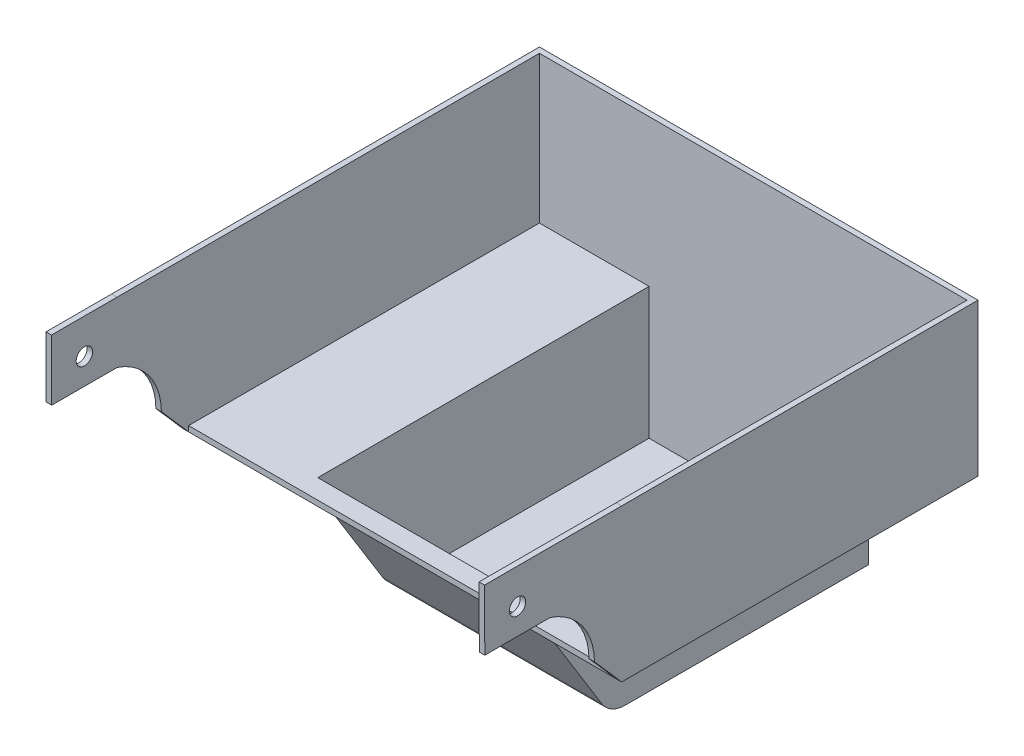
SolidWorks part; units mm, degrees
ref_plane "前视基准面" through (0, 0, 0) normal (0, 0, 1) x (1, 0, 0)
ref_plane "上视基准面" through (0, 0, 0) normal (0, 1, 0) x (1, 0, 0)
ref_plane "右视基准面" through (0, 0, 0) normal (1, 0, 0) x (0, 0, -1)
sketch "草图1" plane through (0, 0, 0) normal (0, 0, 1) x (1, 0, 0)
  line L0 (0, 151.2367) -> (0, -136.5371) construction
  line L1 (-80, 0) -> (-40, 0)
  line L2 (-80, 0) -> (-80, 55.63)
  line L3 (-40, -48) -> (40, -48)
  line L4 (-40, -48) -> (-40, 0)
  line L5 (40, 0) -> (40, -48)
  line L6 (40, 0) -> (80, 0)
  line L7 (-80, 55.63) -> (80, 55.63)
  line L8 (80, 55.63) -> (80, 0)
  point P6 (0, 0)
  point P10 (0, -48)
  dimension "D1" = 160
  dimension "D2" = 55.63
  dimension "D3" = 80
  dimension "D4" = 48
extrude "凸台-拉伸1" add sketch "草图1" along normal blind 124
sketch "草图2" plane through (0, 0, 124) normal (0, 0, 1) x (1, 0, 0)
  line L1 (-80, 0) -> (80, 0)
  line L2 (-80, 0) -> (-80, 55.63)
  line L3 (-80, 55.63) -> (80, 55.63)
  line L4 (80, 0) -> (80, 55.63)
extrude "凸台-拉伸2" add sketch "草图2" along normal blind 6
sketch "草图4" plane through (-40, 0, 0) normal (-1, 0, 0) x (0, 0, 1)
  line L0 (124, 0) -> (97.2566, -43.2585)
  line L1 (124, -48) -> (0, -48) construction
  line L2 (88.7508, -48) -> (88.7508, -53.7264)
  line L3 (88.7508, -53.7264) -> (126.101, -53.7264)
  line L4 (126.101, -53.7264) -> (126.101, 0)
  line L5 (130, 0) -> (0, 0) construction
  line L6 (126.101, 0) -> (124, 0)
  arc A0 (97.2566, -43.2585) -> (88.7508, -48) centre (88.7508, -38) cw
  point P8 (94.3253, -48)
extrude "切除-拉伸1" cut sketch "草图4" against normal through all both and the other way through all
shell "抽壳1" thickness 2 removed face at (0, 55.63, 65)
sketch "草图5" plane through (0, 0, 130) normal (0, 0, 1) x (1, 0, 0)
  line L0 (0, 59.9108) -> (0, -11.2976) construction
sketch "草图6" plane through (0, 0, 128) normal (0, 0, -1) x (-1, 0, 0)
  line L1 (78, 55.63) -> (-78, 55.63)
  line L2 (78, 55.63) -> (78, 2)
  line L3 (78, 2) -> (-78, 2)
  line L4 (-78, 55.63) -> (-78, 2)
extrude "切除-拉伸2" cut sketch "草图6" against normal blind 3
sketch "草图7" plane through (-80, 0, 0) normal (-1, 0, 0) x (0, 0, 1)
  line L0 (130, 55.63) -> (156.0921, 55.63)
  line L1 (156.0921, 55.63) -> (156.0921, 29.8201)
  line L2 (156.0921, 29.8201) -> (130, 0)
  line L3 (130, 0) -> (130, 55.63)
extrude "凸台-拉伸3" add sketch "草图7" against normal blind 2
sketch "草图8" plane through (-80, 0, 0) normal (-1, 0, 0) x (0, 0, 1)
  circle A0 centre (163.3344, 11.15) radius 23.4056
extrude "切除-拉伸3" cut sketch "草图8" against normal through all
sketch "草图9" plane through (-80, 0, 0) normal (-1, 0, 0) x (0, 0, 1)
  line L0 (156.0921, 33.407) -> (179.9388, 33.407)
  line L1 (179.9388, 60.12) -> (179.9388, -0.0003) construction
  line L2 (179.9388, 33.407) -> (180.0265, 55.6297)
  line L3 (180.0265, 55.6297) -> (156.0921, 55.63)
  line L4 (156.0921, 55.63) -> (156.0921, 33.407)
  point P9 (0, 0)
extrude "凸台-拉伸4" add sketch "草图9" against normal blind 2
sketch "草图10" plane through (80, 0, 0) normal (1, 0, 0) x (0, 0, -1)
  line L0 (-130, 55.63) -> (-180.0265, 55.6297)
  line L1 (-180.0265, 55.6297) -> (-179.9388, 33.407)
  line L2 (-179.9388, 33.407) -> (-156.0921, 33.407)
  line L3 (-139.9296, 11.3483) -> (-130, 0)
  line L4 (-130, 0) -> (-139.9296, 11.3483) construction
  line L5 (-130, 0) -> (-130, 55.63)
  arc A0 (-139.9296, 11.3483) -> (-156.0921, 33.407) centre (-163.3344, 11.15) ccw
extrude "凸台-拉伸5" add sketch "草图10" against normal blind 2
sketch "草图11" plane through (80, 0, 0) normal (1, 0, 0) x (0, 0, -1)
  circle A0 centre (-168.0154, 42.8789) radius 3
  dimension "D1" = 6
extrude "切除-拉伸4" cut sketch "草图11" against normal through all
